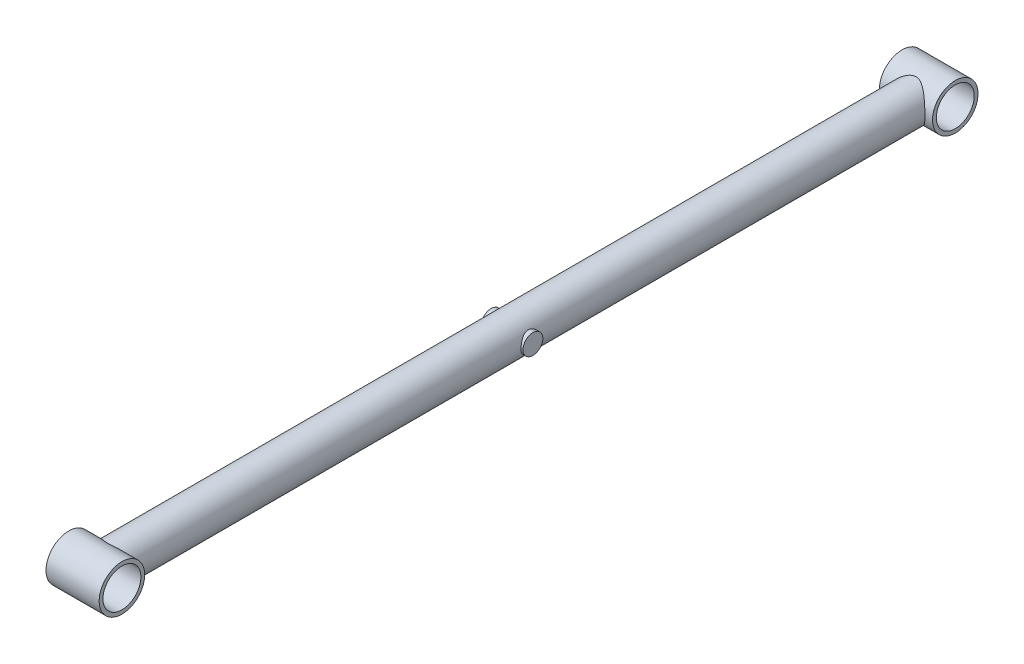
SolidWorks part; units mm, degrees
ref_plane "Front Plane" through (0, 0, 0) normal (0, 0, 1) x (1, 0, 0)
ref_plane "Top Plane" through (0, 0, 0) normal (0, 1, 0) x (1, 0, 0)
ref_plane "Right Plane" through (0, 0, 0) normal (1, 0, 0) x (0, 0, -1)
sketch "Sketch1" plane through (0, 0, 0) normal (1, 0, 0) x (0, 0, -1)
  line L0 (0, 0) -> (-557.6443, 0)
sketch "Sketch2" plane through (0, 0, 0) normal (0, 0, 1) x (1, 0, 0)
  circle A0 centre (0, 0) radius 12.7
sweep "Sweep1" add profiles "Sketch2" path "Sketch1"
sketch "Sketch3" plane through (0, 0, 0) normal (0, 1, 0) x (1, 0, 0)
  line L0 (0, -557.6443) -> (17.78, -557.6443)
  line L1 (-12.7, -557.6443) -> (12.7, -557.6443) construction
  line L2 (0, -557.6443) -> (-17.78, -557.6443)
ref_plane "Plane1" through (0, 0, 278.8221) normal (0, 0, 1) x (1, 0, 0)
sketch "Sketch4" plane through (0, 0, 0) normal (1, 0, 0) x (0, 0, -1)
  circle A0 centre (-557.6443, 0) radius 15.24
sweep "Sweep2" add profiles "Sketch4" path "Sketch3"
sketch "Sketch5" plane through (0, 0, 0) normal (-1, 0, 0) x (0, 0, 1)
  circle A1 centre (557.6443, 0) radius 15.24 construction
  circle A2 centre (557.6443, 0) radius 15.24
extrude "Boss-Extrude1" add sketch "Sketch5" along normal blind 17.78
sketch "Sketch7" plane through (-17.78, 0, 0) normal (-1, 0, 0) x (0, 0, 1)
  circle A0 centre (557.6443, 0) radius 12.7
extrude "Cut-Extrude1" cut sketch "Sketch7" against normal through all
mirror "Mirror1" about plane through (0, 0, 278.8221) normal (0, 0, 1) of "Cut-Extrude1", "Boss-Extrude1", "Sweep2"
sketch "Sketch8" plane through (0, 0, 0) normal (1, 0, 0) x (0, 0, -1)
  line L0 (-557.6443, 0) -> (0, 0) construction
  circle A0 centre (-278.8221, 0) radius 6.65
extrude "Boss-Extrude2" add sketch "Sketch8" along normal blind 13.97 and the other way blind 13.97
